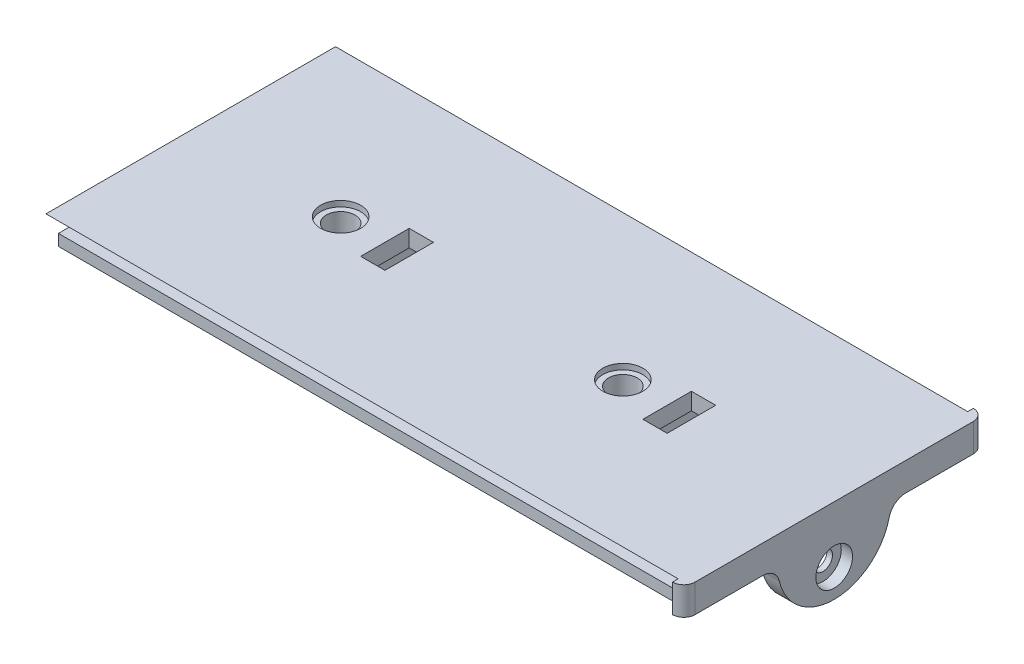
SolidWorks part; units mm, degrees
ref_plane "Front Plane" through (0, 0, 0) normal (0, 0, 1) x (1, 0, 0)
ref_plane "Top Plane" through (0, 0, 0) normal (0, 1, 0) x (1, 0, 0)
ref_plane "Right Plane" through (0, 0, 0) normal (1, 0, 0) x (0, 0, -1)
sketch "Sketch1" plane through (0, 0, 0) normal (0, 1, 0) x (1, 0, 0)
  line L1 (-53.55, 22.65) -> (53.55, 22.65)
  line L2 (-53.55, 22.65) -> (-53.55, -22.65)
  line L3 (-53.55, -22.65) -> (53.55, -22.65)
  line L4 (53.55, 22.65) -> (53.55, -22.65)
  line L5 (-53.55, 22.65) -> (53.55, -22.65) construction
  line L6 (-53.55, -22.65) -> (53.55, 22.65) construction
  point P0 (0, 0)
  dimension "D1" = 107.1
  dimension "D2" = 45.3
extrude "Boss-Extrude1" add sketch "Sketch1" along normal blind 3
sketch "Sketch2" plane through (0, 0, 0) normal (0, -1, 0) x (1, 0, 0)
  line L8 (55.45, -24.55) -> (55.45, 24.55)
  line L9 (55.45, 24.55) -> (-55.45, 24.55)
  line L10 (-55.45, 24.55) -> (-55.45, -24.55)
  line L11 (-55.45, -24.55) -> (55.45, -24.55)
  line L12 (55.45, -24.55) -> (55.45, 24.55)
  line L13 (55.45, 24.55) -> (-55.45, 24.55)
  line L14 (-55.45, 24.55) -> (-55.45, -24.55)
  line L15 (-55.45, -24.55) -> (55.45, -24.55)
  line L16 (51.55, -20.65) -> (51.55, 20.65)
  line L17 (51.55, 20.65) -> (-51.55, 20.65)
  line L18 (-51.55, 20.65) -> (-51.55, -20.65)
  line L19 (-51.55, -20.65) -> (51.55, -20.65)
  line L20 (51.55, -20.65) -> (51.55, 20.65)
  line L21 (51.55, 20.65) -> (-51.55, 20.65)
  line L22 (-51.55, 20.65) -> (-51.55, -20.65)
  line L23 (-51.55, -20.65) -> (51.55, -20.65)
  dimension "D1" = 1.9
  dimension "D2" = 2
extrude "Boss-Extrude2" add sketch "Sketch2" along normal blind 2
sketch "Sketch3" plane through (55.45, 0, 0) normal (1, 0, 0) x (0, 0, -1)
  line L1 (-22.65, 3) -> (-25.65, 3)
  line L2 (-25.65, 3) -> (-22.65, 0)
  line L3 (-22.65, 3) -> (-22.0926, 3)
  line L4 (-22.0926, 3) -> (-22.0926, 0)
  line L5 (-22.0926, 0) -> (-22.65, 0)
  dimension "D1" = 3
sketch "Sketch4" plane through (0, 0, 0) normal (0, 1, 0) x (1, 0, 0)
  line L0 (-55.45, 24.55) -> (55.45, 24.55) construction
  line L1 (-55.45, -24.55) -> (-55.45, 24.55) construction
  line L2 (55.45, -24.55) -> (-55.45, -24.55) construction
  line L3 (-55.45, 24.55) -> (55.45, 24.55)
  line L4 (-55.45, -24.55) -> (-55.45, 24.55)
  line L5 (55.45, -24.55) -> (-55.45, -24.55)
sweep "Sweep3" add profiles "Sketch3" path "Sketch4"
sketch "Sketch5" plane through (53.55, 0, 0) normal (1, 0, 0) x (0, 0, -1)
  line L4 (22.0926, 0) -> (22.0926, 3)
  line L5 (22.0926, 3) -> (-22.0926, 3)
  line L6 (-22.0926, 3) -> (-22.0926, 0)
  line L7 (-22.0926, 0) -> (22.0926, 0)
  line L8 (22.0926, 0) -> (22.0926, 3)
  line L9 (22.0926, 3) -> (-22.0926, 3)
  line L10 (-22.0926, 3) -> (-22.0926, 0)
  line L11 (-22.0926, 0) -> (22.0926, 0)
  dimension "D1" = 0
extrude "Boss-Extrude3" add sketch "Sketch5" along normal up to surface (1.9 mm away) up to face at (55.45, 1, 0)
sketch "Sketch6" plane through (55.45, 0, 0) normal (1, 0, 0) x (0, 0, -1)
  line L0 (24.55, -2) -> (-24.55, -2) construction
  line L1 (-26.65, 3) -> (26.65, 3)
  line L2 (-26.65, 3) -> (-26.65, -2)
  line L3 (-26.65, -2) -> (26.65, -2)
  line L4 (26.65, 3) -> (26.65, -2)
  point P6 (0, 0)
  point P9 (0, 0)
  point P11 (0, 3)
  point P12 (0, -2)
  dimension "D1" = 53.3
extrude "Boss-Extrude4" add sketch "Sketch6" along normal blind 2
fillet "Fillet1" radius 2 2 edges at (57.45, 0.5, 26.65) (57.45, 0.5, -26.65)
sketch "Sketch7" plane through (57.45, 0, 0) normal (1, 0, 0) x (0, 0, -1)
  line L0 (-24.65, -2) -> (24.65, -2) construction
  line L1 (-10, -2) -> (10, -2)
  arc A0 (-10, -2) -> (10, -2) centre (0, -2) ccw
  dimension "D1" = 20
extrude "Boss-Extrude5" add sketch "Sketch7" against normal blind 3
fillet "Fillet2" radius 3 2 edges at (55.95, -2, 10) (55.95, -2, -10)
hole_wizard "CBORE for M3 Cheese Head Screw1" positions "3DSketch1" profile "Sketch8" counterbore size "M3" standard "AS" end condition up to next
sketch3d "3DSketch1"
  line L0 (57.45, -2, 12.6491) -> (57.45, -2, -12.6491) construction
  line L2 (57.45, -2, 0) -> (57.45, -12, 0) construction
  arc A0 (57.45, -4.3077, 9.7301) -> (57.45, -4.3077, -9.7301) centre (57.45, -2, 0) ccw construction
  point P0 (57.45, -7, 0)
  point P12 (67.45, -2, 0)
  point P14 (0, 0, 0)
  point P15 (57.45, -7, 0)
sketch "Sketch8" plane through (57.45, -7, 0) normal (0, 1, 0) x (0, 0, -1)
  line L0 (0, 0) -> (0, 3)
  line L1 (0, 3) -> (1.7, 3)
  line L3 (1.7, 3) -> (1.7, 2)
  line L4 (1.7, 2) -> (3.25, 2)
  line L5 (3.25, 2) -> (3.25, 0)
  line L7 (3.25, 0) -> (0, 0)
  line L11 (0, -6.35) -> (0, 107.95) construction
  dimension "Thru Hole Dia." = 3.4
  dimension "Thru Hole Depth" = 3
  dimension "C'Bore Dia." = 6.5
  dimension "C'Bore Depth" = 2
sketch "Sketch9" plane through (0, 0, 0) normal (0, -1, 0) x (1, 0, 0)
  line L0 (27.85, 4.3) -> (32.15, 4.3)
  line L1 (27.85, 4.3) -> (27.85, -4.3)
  line L2 (27.85, -4.3) -> (32.15, -4.3)
  line L3 (32.15, 4.3) -> (32.15, -4.3)
  line L4 (0, 20.65) -> (0, -20.65) construction
  line L5 (51.55, 20.65) -> (-51.55, 20.65) construction
  line L6 (-51.55, -20.65) -> (51.55, -20.65) construction
  line L7 (-51.55, 0) -> (51.55, 0) construction
  line L8 (-51.55, 20.65) -> (-51.55, -20.65) construction
  line L9 (51.55, -20.65) -> (51.55, 20.65) construction
  line L10 (-22.15, 4.3) -> (-17.85, 4.3)
  line L11 (-22.15, 4.3) -> (-22.15, -4.3)
  line L12 (-22.15, -4.3) -> (-17.85, -4.3)
  line L13 (-17.85, 4.3) -> (-17.85, -4.3)
  circle A0 centre (20, 0) radius 2.55
  circle A1 centre (-30, 0) radius 2.55
  point P18 (0, 0)
  point P19 (27.85, 0)
  point P20 (30, 4.3)
  point P27 (-22.15, 0)
  point P28 (-20, 4.3)
  point P29 (0, 0)
  dimension "D4" = 5.1
  dimension "D5" = 20
  dimension "D8" = 5.1
  dimension "D1" = 10
  dimension "D2" = 4.3
  dimension "D3" = 8.6
  dimension "D6" = 4.3
  dimension "D7" = 8.6
  dimension "D9" = 10
  dimension "D10" = 20
extrude "Cut-Extrude1" cut sketch "Sketch9" against normal through all
sketch "Sketch11" plane through (0, 0, 0) normal (0, -1, 0) x (1, 0, 0)
  line L0 (-20, 4.3) -> (-20, -4.3) construction
  line L1 (-17.85, 4.3) -> (-22.15, 4.3) construction
  line L2 (-22.15, -4.3) -> (-17.85, -4.3) construction
  line L3 (-14.25, -7.5) -> (-16.25, -7.5)
  line L4 (-25.75, 7.5) -> (-23.75, 7.5)
  line L5 (-25.75, 7.5) -> (-25.75, -7.5)
  line L6 (-25.75, -7.5) -> (-23.75, -7.5)
  line L7 (-23.75, 7.5) -> (-23.75, -7.5)
  line L8 (-16.25, 7.5) -> (-16.25, -7.5)
  line L9 (-14.25, 7.5) -> (-16.25, 7.5)
  line L10 (-14.25, 7.5) -> (-14.25, -7.5)
  line L11 (30, 4.3) -> (30, -4.3) construction
  line L12 (35.5165, -7.5) -> (33.5165, -7.5)
  line L13 (24.4835, 7.5) -> (26.4835, 7.5)
  line L14 (24.4835, 7.5) -> (24.4835, -7.5)
  line L15 (24.4835, -7.5) -> (26.4835, -7.5)
  line L16 (26.4835, 7.5) -> (26.4835, -7.5)
  line L17 (33.5165, 7.5) -> (33.5165, -7.5)
  line L18 (35.5165, 7.5) -> (33.5165, 7.5)
  line L19 (35.5165, 7.5) -> (35.5165, -7.5)
  line L20 (32.15, 4.3) -> (27.85, 4.3) construction
  line L21 (27.85, -4.3) -> (32.15, -4.3) construction
  circle A0 centre (-30, 0) radius 2.55 construction
  circle A1 centre (-30, 0) radius 2.55
  circle A2 centre (-30, 0) radius 3.55
  circle A3 centre (20, 0) radius 2.55 construction
  circle A4 centre (20, 0) radius 2.55
  circle A5 centre (20, 0) radius 3.55
  point P10 (-23.75, 0)
  point P11 (-20, 0)
  point P22 (26.4835, 0)
  point P23 (30, 0)
  point P28 (0, 0)
  point P31 (30, 4.3)
  point P32 (0, 0)
  dimension "D1" = 15
  dimension "D2" = 7.5
  dimension "D3" = 2
  dimension "D4" = 15
  dimension "D5" = 1
  dimension "D6" = 1
extrude "Boss-Extrude6" add sketch "Sketch11" along normal blind 5
sketch "Sketch12" plane through (0, 3, 0) normal (0, 1, 0) x (1, 0, 0)
  circle A4 centre (-30, 0) radius 3.55
  circle A5 centre (20, 0) radius 3.55
extrude "Cut-Extrude2" cut sketch "Sketch12" against normal blind 1
